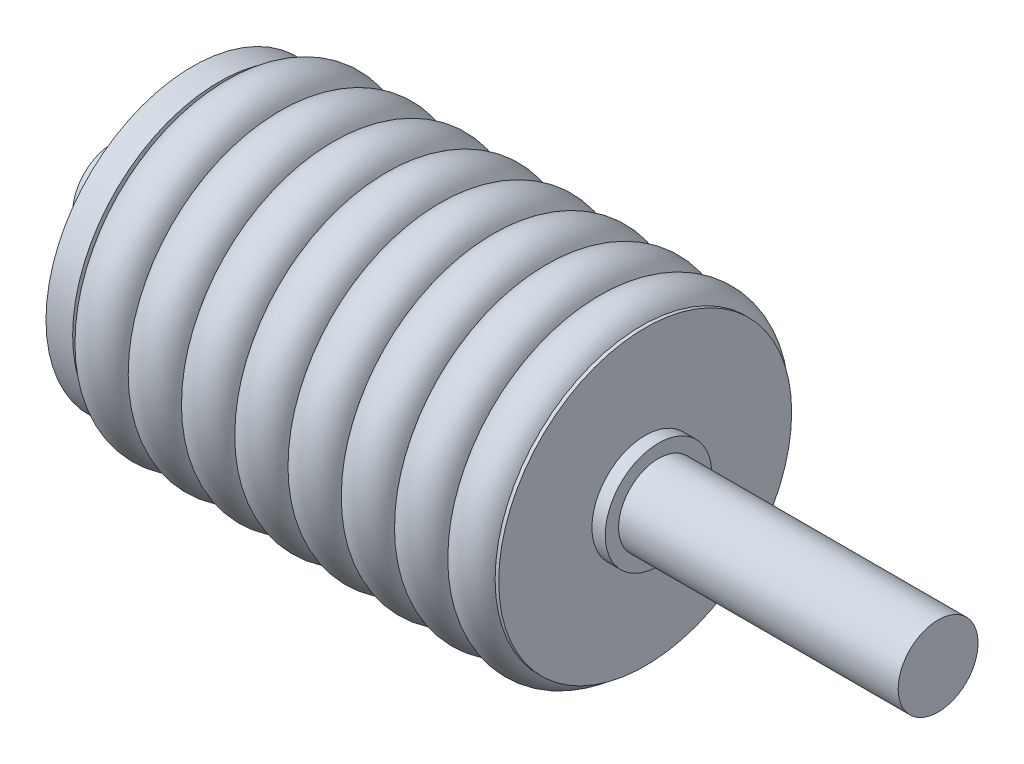
SolidWorks part; units mm, degrees
material "1060 合金"
ref_plane "前视基准面" through (0, 0, 0) normal (0, 0, 1) x (1, 0, 0)
ref_plane "上视基准面" through (0, 0, 0) normal (0, 1, 0) x (1, 0, 0)
ref_plane "右视基准面" through (0, 0, 0) normal (1, 0, 0) x (0, 0, -1)
sketch "草图2" plane through (0, 0, 0) normal (0, 0, 1) x (1, 0, 0)
  line L0 (32, 11) -> (34, 11)
  line L1 (-6, 0) -> (56, 0)
  line L2 (0, 4) -> (0, 11)
  line L3 (0, 11) -> (2, 11)
  line L4 (34, 4) -> (34, 11)
  line L5 (-1, 3) -> (-6, 3)
  line L6 (2, 11) -> (2, 8)
  line L7 (2, 8) -> (32, 8)
  line L8 (32, 11) -> (32, 8)
  line L9 (-6, 3) -> (-6, 0)
  line L10 (35, 3) -> (56, 3)
  line L11 (56, 3) -> (56, 0)
  line L12 (-1, 3) -> (-1, 4)
  line L13 (-1, 4) -> (0, 4)
  line L14 (34, 4) -> (35, 4)
  line L15 (35, 4) -> (35, 3)
  circle A0 centre (4.5, 10.5) radius 2.5 construction
  dimension "D3" = 5
  dimension "D1" = 2
  dimension "D2" = 2
  dimension "D4" = 3
  dimension "D5" = 8
  dimension "D6" = 30
  dimension "D7" = 3
  dimension "D8" = 3
  dimension "D9" = 5
  dimension "D10" = 1
  dimension "D11" = 1
  dimension "D12" = 1
  dimension "D13" = 1
  dimension "D14" = 21
revolve "旋转1" add sketch "草图2" angle 360 about L1
sketch "草图5" plane through (0, 0, 0) normal (0, 0, 1) x (1, 0, 0)
  line L0 (32, 8) -> (2, 8) construction
  line L1 (32, 8) -> (2, 8) construction
  line L2 (2, -11) -> (2, 11) construction
  line L3 (0, 0) -> (37.0214, 0) construction
  circle A0 centre (4, 10) radius 2
  dimension "D1" = 4
revolve "旋转2" add sketch "草图5" angle 360 about L3
pattern_linear "阵列(线性)2" count 8 spacing 4 along (1, 0, 0) of bodies 116
